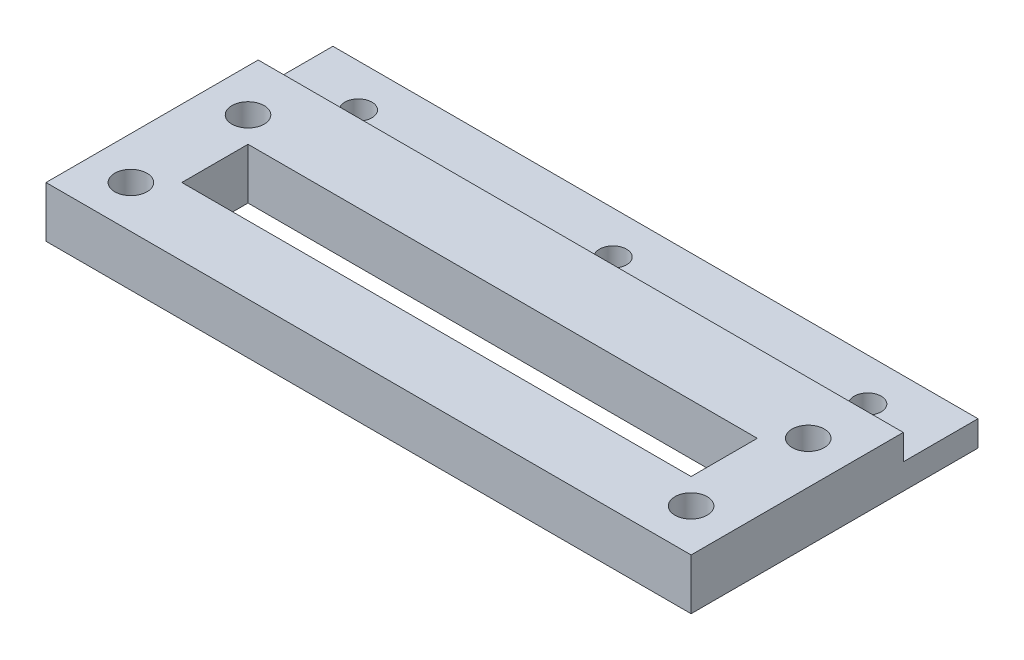
SolidWorks part; units mm, degrees
ref_plane "前视基准面" through (0, 0, 0) normal (0, 0, 1) x (1, 0, 0)
ref_plane "上视基准面" through (0, 0, 0) normal (0, 1, 0) x (1, 0, 0)
ref_plane "右视基准面" through (0, 0, 0) normal (1, 0, 0) x (0, 0, -1)
other "Configuration Table"
sketch "草图1" plane through (0, 0, 0) normal (0, 1, 0) x (1, 0, 0)
  line L0 (-5, 5) -> (-5, -18.8)
  line L1 (0, 0) -> (66, 0)
  line L2 (0, 0) -> (0, -13.8)
  line L3 (0, -13.8) -> (66, -13.8)
  line L4 (66, 0) -> (66, -13.8)
  line L5 (-5, -18.8) -> (71, -18.8)
  line L6 (71, 5) -> (71, -18.8)
  line L7 (-5, 5) -> (71, 5)
  circle A0 centre (0, 0) radius 1.9
  circle A1 centre (0, -13.8) radius 1.9
  circle A2 centre (66, 0) radius 1.9
  circle A3 centre (66, -13.8) radius 1.9
  dimension "D3" = 3.8
  dimension "D4" = 3.8
  dimension "D5" = 3.8
  dimension "D6" = 3.8
  dimension "D1" = 13.8
  dimension "D2" = 66
  dimension "D7" = 5
extrude "凸台-拉伸1" add sketch "草图1" along normal blind 3 contours A3 L4 A2 L1 A0 L2 A1 L3 | L7 L0 L5 L6 A3 L3 A1 L2 A0 L1 A2 L4 region at (33, 0, -4.2036) region at (33, 0, 6.9)
sketch "草图3" plane through (0, 0, -5) normal (0, 0, -1) x (-1, 0, 0)
  line L4 (-71, 0) -> (5, 0)
  line L5 (5, 0) -> (5, 3)
  line L6 (5, 3) -> (-71, 3)
  line L7 (-71, 3) -> (-71, 0)
  line L8 (-71, 0) -> (5, 0)
  line L9 (5, 0) -> (5, 3)
  line L10 (5, 3) -> (-71, 3)
  line L11 (-71, 3) -> (-71, 0)
  dimension "D1" = 0
extrude "凸台-拉伸2" add sketch "草图3" along normal blind 10
sketch "草图4" plane through (0, 3, 0) normal (0, 1, 0) x (1, 0, 0)
  line L0 (-5, 15) -> (-5, -18.8) construction
  line L1 (71, 15) -> (71, -18.8) construction
  line L2 (-5, 15) -> (71, 15) construction
  circle A0 centre (3, 10) radius 1.6
  circle A1 centre (33, 10) radius 1.6
  circle A2 centre (63, 10) radius 1.6
  dimension "D1" = 3.2
  dimension "D2" = 3.2
  dimension "D3" = 3.2
  dimension "D4" = 8
  dimension "D5" = 8
  dimension "D6" = 5
  dimension "D7" = 5
  dimension "D8" = 5
  dimension "D9" = 30
extrude "切除-拉伸1" cut sketch "草图4" against normal blind 10
sketch "草图5" plane through (0, 3, 0) normal (0, 1, 0) x (1, 0, 0)
  line L0 (3, -3) -> (3, -10.8)
  line L1 (0, 0) -> (66, 0)
  line L2 (0, 0) -> (0, -13.8)
  line L3 (0, -13.8) -> (66, -13.8)
  line L4 (66, 0) -> (66, -13.8)
  line L5 (3, -10.8) -> (63, -10.8)
  line L6 (63, -3) -> (63, -10.8)
  line L7 (3, -3) -> (63, -3)
  dimension "D1" = 3
extrude "切除-拉伸2" cut sketch "草图5" against normal blind 10 contours L0 L5 L6 L7
sketch "草图6" plane through (0, 3, 0) normal (0, 1, 0) x (1, 0, 0)
  line L0 (-5, 15) -> (-5, -18.8) construction
  line L1 (-5, 6.2) -> (71, 6.2)
  line L2 (-5, 6.2) -> (-5, -18.8)
  line L3 (-5, -18.8) -> (71, -18.8)
  line L4 (71, 6.2) -> (71, -18.8)
  line L9 (3, -3) -> (3, -10.8)
  line L10 (63, -3) -> (3, -3)
  line L11 (63, -10.8) -> (63, -3)
  line L12 (3, -10.8) -> (63, -10.8)
  line L13 (3, -3) -> (3, -10.8)
  line L14 (63, -3) -> (3, -3)
  line L15 (63, -10.8) -> (63, -3)
  line L16 (3, -10.8) -> (63, -10.8)
  circle A1 centre (66, -13.8) radius 1.9
  circle A2 centre (66, -13.8) radius 1.9
  circle A3 centre (66, 0) radius 1.9
  circle A4 centre (66, 0) radius 1.9
  circle A5 centre (0, -13.8) radius 1.9
  circle A6 centre (0, -13.8) radius 1.9
  circle A7 centre (0, 0) radius 1.9
  circle A8 centre (0, 0) radius 1.9
  circle A9 centre (63, 10) radius 1.6
  circle A10 centre (63, 10) radius 1.6
  circle A11 centre (33, 10) radius 1.6
  circle A12 centre (33, 10) radius 1.6
  circle A13 centre (3, 10) radius 1.6
  circle A14 centre (3, 10) radius 1.6
  circle M19 centre (66, -13.8) radius 1.9
  circle M20 centre (66, 0) radius 1.9
  circle M21 centre (0, -13.8) radius 1.9
  circle M22 centre (0, 0) radius 1.9
  line M27 (3, -10.8) -> (3, -3)
  line M28 (3, -3) -> (63, -3)
  line M29 (63, -3) -> (63, -10.8)
  line M30 (63, -10.8) -> (3, -10.8)
  dimension "D1" = 25
  dimension "D2" = 0
  dimension "D3" = 0
  dimension "D4" = 0
  dimension "D5" = 0
  dimension "D6" = 0
  dimension "D7" = 0
  dimension "D8" = 0
  dimension "D9" = 0
extrude "凸台-拉伸3" add sketch "草图6" along normal blind 3 contours M27 M30 M29 M28 | M22 | M21 | M19 | M20 | L2 L1 L4 L3 region at (33, 3, 6.9) region at (66, 3, 13.8) region at (66, 3, 0) region at (0, 3, 13.8) region at (0, 3, 0)
